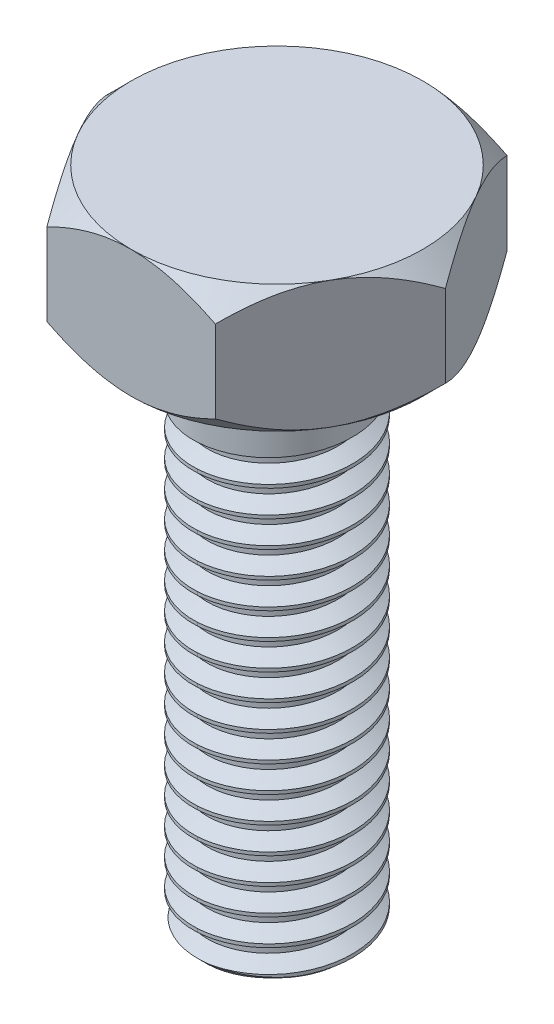
SolidWorks part; units mm, degrees
ref_plane "Front Plane" through (0, 0, 0) normal (0, 0, 1) x (1, 0, 0)
ref_plane "Top Plane" through (0, 0, 0) normal (0, 1, 0) x (1, 0, 0)
ref_plane "Right Plane" through (0, 0, 0) normal (1, 0, 0) x (0, 0, -1)
sketch "Sketch1" plane through (0, 0, 0) normal (0, 1, 0) x (1, 0, 0)
  line L1 (3.1754, 0) -> (1.5877, 2.75)
  line L2 (1.5877, 2.75) -> (-1.5877, 2.75)
  line L3 (-1.5877, 2.75) -> (-3.1754, 0)
  line L4 (-3.1754, 0) -> (-1.5877, -2.75)
  line L5 (-1.5877, -2.75) -> (1.5877, -2.75)
  line L6 (1.5877, -2.75) -> (3.1754, 0)
  circle A0 centre (0, 0) radius 2.75 construction
  dimension "D1" = 5.5
extrude "Boss-Extrude1" add sketch "Sketch1" along normal blind 2.4
sketch "Sketch11" plane through (0, 0, 0) normal (0, -1, 0) x (1, 0, 0)
  line L0 (1.5877, 2.75) -> (3.1754, 0) construction
  circle A0 centre (0, 0) radius 2.75
extrude "Cut-Extrude1" cut sketch "Sketch11" against normal through all draft 45 flip side to cut
sketch "Sketch12" plane through (0, 2.4, 0) normal (0, 1, 0) x (1, 0, 0)
  line L0 (-1.5877, 2.75) -> (-3.1754, 0) construction
  circle A0 centre (0, 0) radius 2.75
extrude "Cut-Extrude2" cut sketch "Sketch12" against normal through all draft 45 flip side to cut
sketch "Sketch2" plane through (0, 0, 0) normal (0, -1, 0) x (1, 0, 0)
  circle A0 centre (0, 0) radius 1.5
  dimension "D1" = 3
extrude "Boss-Extrude2" add sketch "Sketch2" along normal blind 10
chamfer "Chamfer1" distance 0.2 angle 45 1 edges at (0, -10, -1.5)
thread "Thread1" pitch 0.5 method cut profile "Thread Profile2" start angle 0, offset 1, length 0, pitch 0.5, diameter 3
ref_plane "Plane2" through (-1.5, -1, 0) normal (0, 0, 1) x (-1, 0, 0)
sketch "Thread Profile2" plane through (-1.5, -1, 0) normal (0, 0, 1) x (-1, 0, 0)
  line L0 (0, 0) -> (0, 0.5) construction
  line L11 (0, 0) -> (0, 0.4375)
  line L12 (0, 0.4375) -> (-0.2706, 0.2812)
  line L13 (-0.2706, 0.2812) -> (-0.2706, 0.1562)
  line L15 (-0.2706, 0.1562) -> (0, 0)
  line L17 (-0.2706, 0.2187) -> (0, 0.2187) construction
  point P2 (0, 0)
  dimension "Pitch" = 0.5
  dimension "Profile_Angle" = 60
  dimension "Profile_Land" = 0.125
  dimension "Profile_Height" = 0.2706
sketch "Sketch13" plane through (0, 0, 0) normal (0, 0, -1) x (-1, 0, 0)
  line L4 (1.5, -1) -> (1.2294, -1.1562)
  line L5 (1.2294, -1.1562) -> (1.2294, -1.2812)
  line L6 (1.2294, -1.2812) -> (1.5, -1.4375)
  line L7 (1.5, -1.4375) -> (1.5, -1)
  line L8 (1.5, -1) -> (1.2294, -1.1562)
  line L9 (1.2294, -1.1562) -> (1.2294, -1.2812)
  line L10 (1.2294, -1.2812) -> (1.5, -1.4375)
  line L11 (1.5, -1.4375) -> (1.5, -1)
  dimension "D2" = 0.2706
  dimension "D1" = 0
extrude "Cut-Extrude3" cut sketch "Sketch13" against normal through all
